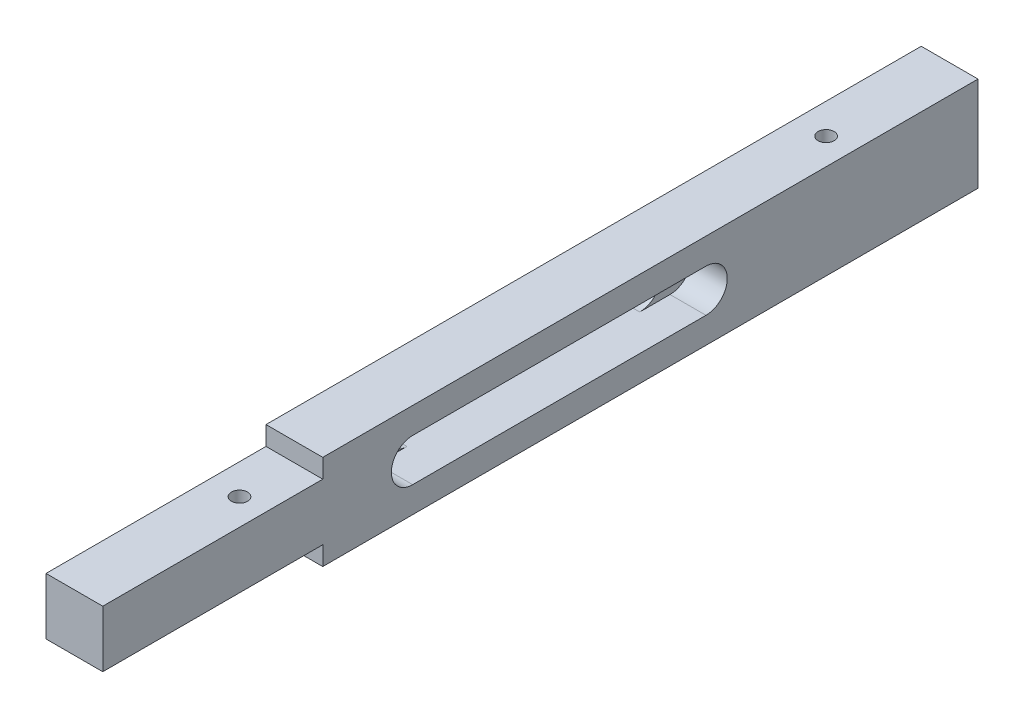
SolidWorks part; units mm, degrees
ref_plane "前视基准面" through (0, 0, 0) normal (0, 0, 1) x (1, 0, 0)
ref_plane "上视基准面" through (0, 0, 0) normal (0, 1, 0) x (1, 0, 0)
ref_plane "右视基准面" through (0, 0, 0) normal (1, 0, 0) x (0, 0, -1)
sketch "草图1" plane through (0, 0, 0) normal (1, 0, 0) x (0, 0, -1)
  line L0 (-15.5, 0) -> (15.5, 0) construction
  line L1 (-25, 5) -> (25, 5)
  line L2 (-25, 5) -> (-25, 3)
  line L3 (-25, -5) -> (25, -5)
  line L4 (25, 5) -> (25, 3)
  line L5 (-25, 5) -> (25, -5) construction
  line L6 (-25, -5) -> (25, 5) construction
  line L7 (-15.5, 2.25) -> (15.5, 2.25)
  line L8 (-15.5, -2.25) -> (15.5, -2.25)
  line L9 (-12.3, 0) -> (12.3, 0) construction
  line L10 (-12.3, 2.25) -> (12.3, 2.25)
  line L11 (-12.3, -2.25) -> (12.3, -2.25)
  line L12 (25, 3) -> (48.25, 3)
  line L13 (-48.25, 3) -> (-25, 3)
  line L14 (-48.25, 3) -> (-48.25, -3)
  line L15 (-48.25, -3) -> (-25, -3)
  line L16 (48.25, 3) -> (48.25, -3)
  line L17 (-48.25, 3) -> (48.25, -3) construction
  line L18 (-48.25, -3) -> (48.25, 3) construction
  line L19 (25, -3) -> (48.25, -3)
  line L20 (-25, -3) -> (-25, -5)
  line L21 (25, -3) -> (25, -5)
  arc A0 (-15.5, 2.25) -> (-15.5, -2.25) centre (-15.5, 0) ccw
  arc A1 (15.5, -2.25) -> (15.5, 2.25) centre (15.5, 0) ccw
  arc A2 (-12.3, 2.25) -> (-12.3, -2.25) centre (-12.3, 0) ccw
  arc A3 (12.3, -2.25) -> (12.3, 2.25) centre (12.3, 0) ccw
  point P0 (0, 0)
  point P8 (0, 0)
  point P14 (0, 0)
  point P20 (0, 0)
  point P29 (0, 0)
  dimension "D1" = 31
  dimension "D2" = 24.6
  dimension "D3" = 4.5
  dimension "D4" = 10
  dimension "D5" = 23.25
  dimension "D6" = 96.5
  dimension "D7" = 6
extrude "凸台-拉伸1" add sketch "草图1" against normal blind 6 contours L2 L13 L14 L15 L20 L3 L21 L19 L16 L12 L4 L1
extrude "切除-拉伸1" cut sketch "草图1<3>" against normal blind 3.8 contours A0 L8 A1 L7
sketch "草图1<3>" plane through (0, 0, 0) normal (1, 0, 0) x (0, 0, -1) same geometry as "草图1"
extrude "切除-拉伸2" cut sketch "草图1<4>" against normal through all contours A2 L11 A3 L10
sketch "草图1<4>" plane through (0, 0, 0) normal (1, 0, 0) x (0, 0, -1) same geometry as "草图1"
sketch "草图3" plane through (0, 0, -48.25) normal (0, 0, -1) x (-1, 0, 0)
  line L1 (-7.6413, 9.5848) -> (10.8952, 9.5848)
  line L2 (-7.6413, 9.5848) -> (-7.6413, -6.0527)
  line L3 (-7.6413, -6.0527) -> (10.8952, -6.0527)
  line L4 (10.8952, 9.5848) -> (10.8952, -6.0527)
extrude "切除-拉伸3" cut sketch "草图3" against normal blind 4
sketch "草图4" plane through (0, 0, -25) normal (0, 0, -1) x (-1, 0, 0)
  line L1 (0, 5) -> (6, 5)
  line L2 (0, 5) -> (0, -5)
  line L3 (0, -5) -> (6, -5)
  line L4 (6, 5) -> (6, -5)
extrude "凸台-拉伸2" add sketch "草图4" along normal up to surface (19.25 mm away) up to face at (-3, 0, -44.25)
sketch "草图5" plane through (0, -5, 0) normal (0, -1, 0) x (1, 0, 0)
  circle A0 centre (-2.8, -31) radius 1.2 construction
  circle A1 centre (-2.8, -31) radius 1.2 construction
  circle A2 centre (-2.8, 31) radius 1.2 construction
  circle A3 centre (-2.8, 31) radius 1.2 construction
  circle A4 centre (-2.8, 31) radius 0.85
  circle A5 centre (-2.8, -31) radius 0.85
  dimension "D1" = 1.7
extrude "切除-拉伸4" cut sketch "草图5" against normal through all
sketch "草图6" plane through (0, 0, -44.25) normal (0, 0, -1) x (-1, 0, 0)
  circle A2 centre (3, 0) radius 0.85
  circle A3 centre (3, 0) radius 1.2 construction
  dimension "D1" = 1.7
extrude "切除-拉伸5" cut sketch "草图6" against normal blind 6
